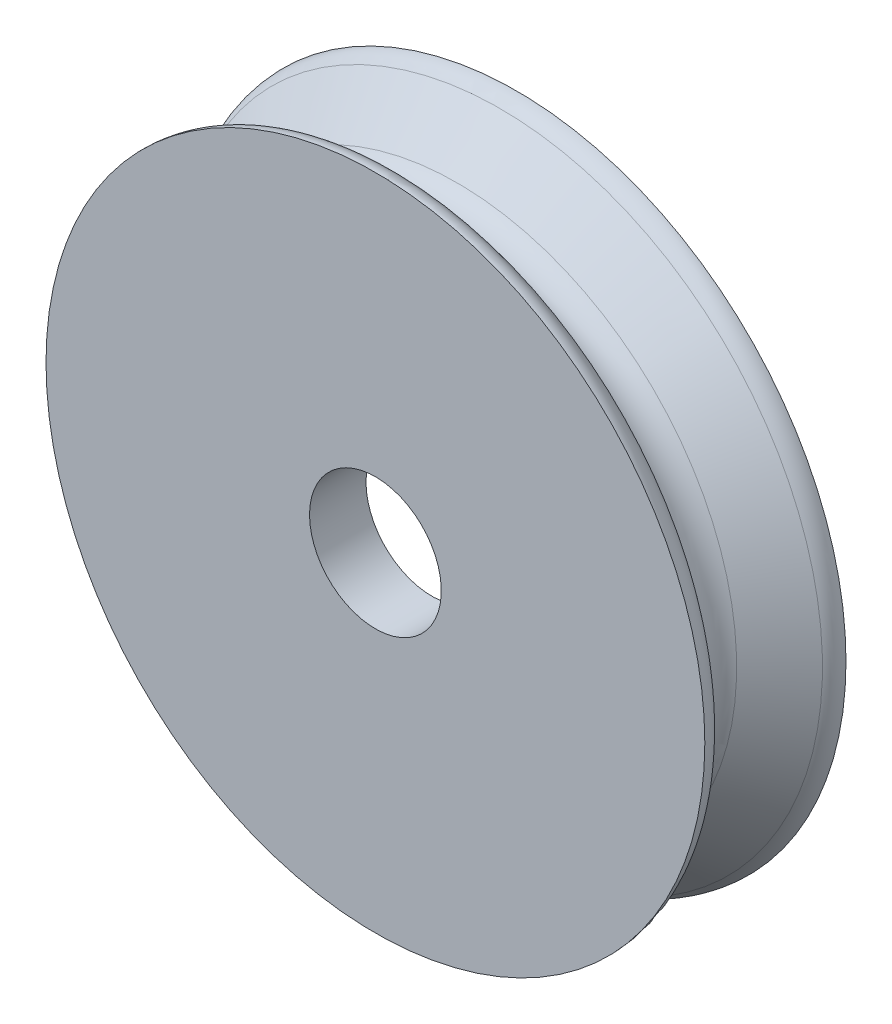
SolidWorks part; units mm, degrees
ref_plane "Front Plane" through (0, 0, 0) normal (0, 0, 1) x (1, 0, 0)
ref_plane "Top Plane" through (0, 0, 0) normal (0, 1, 0) x (1, 0, 0)
ref_plane "Right Plane" through (0, 0, 0) normal (1, 0, 0) x (0, 0, -1)
sketch "Sketch1" plane through (0, 0, 0) normal (1, 0, 0) x (0, 0, -1)
  line L0 (-3.6, 2.8) -> (-6, 2.8)
  line L1 (-6, 2.8) -> (-6, 14)
  line L2 (-5.0341, 13.2588) -> (-4.8308, 12.5002)
  line L3 (-2.5304, 11.8838) -> (-0.7071, 13.7071)
  line L4 (0, 14) -> (0, 12.1515)
  line L5 (0, 0) -> (-11.3925, 0) construction
  line L6 (0, 12.1515) -> (-3.6, 8.5515)
  line L7 (-3.6, 8.5515) -> (-3.6, 2.8)
  arc A0 (-6, 14) -> (-5.0341, 13.2588) centre (-6, 13) cw
  arc A1 (-4.8308, 12.5002) -> (-2.5304, 11.8838) centre (-3.5027, 12.8561) ccw
  arc A2 (-0.7071, 13.7071) -> (0, 14) centre (0, 13) cw
  dimension "D1" = 2.8
  dimension "D5" = 1.375
  dimension "D6" = 14
  dimension "D7" = 1
  dimension "D2" = 6
  dimension "D3" = 15
  dimension "D4" = 45
  dimension "D8" = 1.6
  dimension "D9" = 3.6
revolve "Revolve1" add sketch "Sketch1" angle 360 about L5
ref_plane "Plane1" through (0, 0, 3.5027) normal (0, 0, -1) x (-1, 0, 0)
